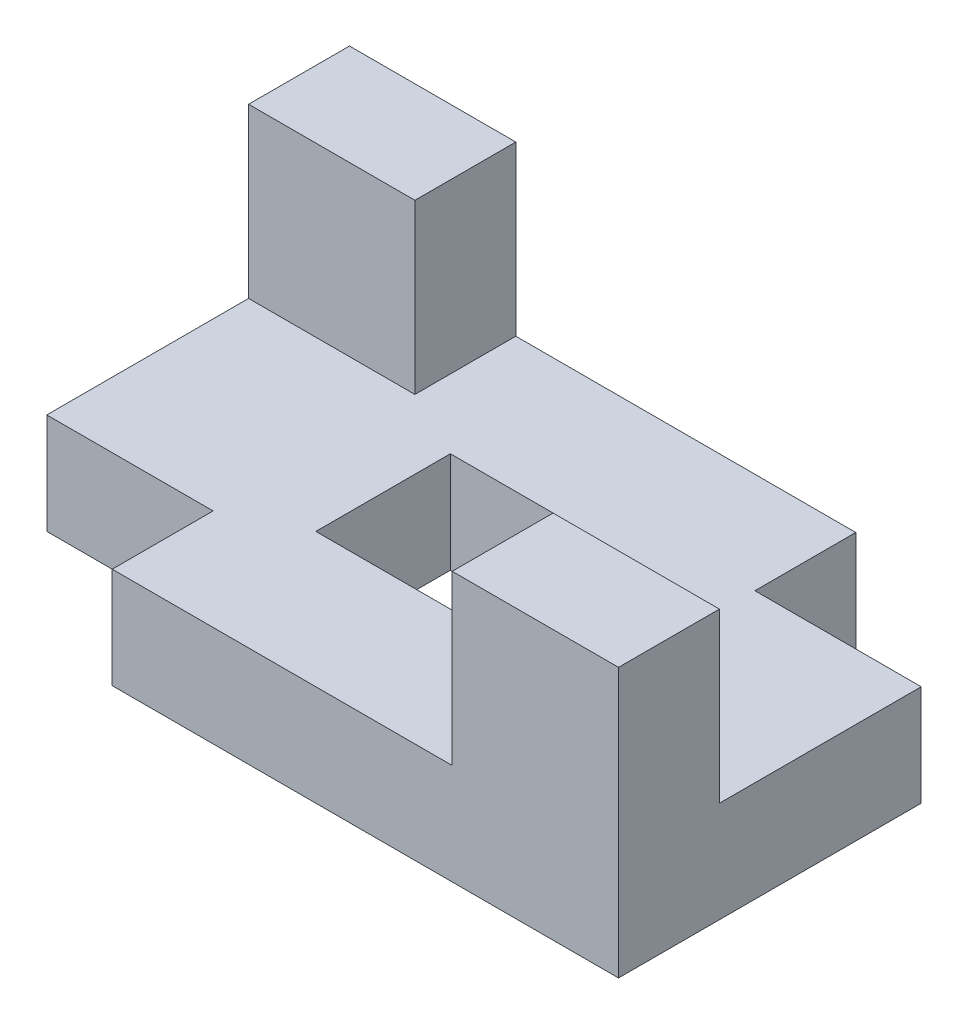
SolidWorks part; units mm, degrees
ref_plane "Front Plane" through (0, 0, 0) normal (0, 0, 1) x (1, 0, 0)
ref_plane "Top Plane" through (0, 0, 0) normal (0, 1, 0) x (1, 0, 0)
ref_plane "Right Plane" through (0, 0, 0) normal (1, 0, 0) x (0, 0, -1)
sketch "Sketch1" plane through (0, 0, 0) normal (0, 1, 0) x (1, 0, 0)
  line L0 (0, 0) -> (0, 61.2785) construction
  line L1 (-50, 30) -> (50, 30)
  line L2 (-50, 30) -> (-50, -30)
  line L3 (-50, -30) -> (50, -30)
  line L4 (50, 30) -> (50, -30)
  line L5 (-50, 30) -> (-25.2735, 30)
  line L6 (-50, 30) -> (-50, 15)
  line L7 (-50, 15) -> (-25.2735, 15)
  line L8 (-25.2735, 30) -> (-25.2735, 15)
  line L9 (0, 0) -> (147.7716, 0) construction
  line L10 (50, 15) -> (25.2735, 15)
  line L11 (25.2735, 30) -> (25.2735, 15)
  line L12 (50, 30) -> (25.2735, 30)
  line L13 (50, 30) -> (50, 15)
  line L14 (50, -30) -> (25.2735, -30)
  line L15 (25.2735, -30) -> (25.2735, -15)
  line L16 (50, -15) -> (25.2735, -15)
  line L17 (50, -30) -> (50, -15)
  line L18 (-50, -15) -> (-25.2735, -15)
  line L19 (-25.2735, -30) -> (-25.2735, -15)
  line L20 (-50, -30) -> (-25.2735, -30)
  line L21 (-50, -30) -> (-50, -15)
  line L23 (-15, 10) -> (15, 10)
  line L24 (-15, 10) -> (-15, -10)
  line L25 (-15, -10) -> (15, -10)
  line L26 (15, 10) -> (15, -10)
  dimension "D1" = 50
  dimension "D2" = 30
  dimension "D3" = 100
  dimension "D4" = 60
  dimension "D5" = 24.7265
  dimension "D6" = 15
  dimension "D7" = 35
  dimension "D8" = 20
  dimension "D9" = 30
  dimension "D10" = 20
extrude "Boss-Extrude1" add sketch "Sketch1" along normal blind 15 contours L8 L1 L2 L7 | L19 L3 L15 L16 L4 L10 L11 L1 L8 L7 L2 L18 L23 L26 L25 L24 | L26 L23 L24 L25 | L1 L11 L10 L4 | L4 L16 L15 L3 | L3 L19 L18 L2 region at (-37.6368, 0, -22.5) region at (0, 0, -28.8338) region at (37.6368, 0, -22.5) region at (-37.6368, 0, 22.5) region at (37.6368, 0, 22.5) region at (0, 0, 0)
extrude "Boss-Extrude2" add sketch "Sketch1<4>" along normal blind 40 contours L6 L7 L8 L5 | L17 L16 L15 L14
sketch "Sketch1<4>" plane through (0, 0, 0) normal (0, 1, 0) x (1, 0, 0) same geometry as "Sketch1"
extrude "Cut-Extrude1" cut sketch "Sketch1<5>" along normal blind 40 contours L3 L19 L18 L2 | L1 L11 L10 L4 region at (37.6368, 0, -22.5) region at (-37.6368, 0, 22.5)
sketch "Sketch1<5>" plane through (0, 0, 0) normal (0, 1, 0) x (1, 0, 0) same geometry as "Sketch1"
extrude "Cut-Extrude2" cut sketch "Sketch1<6>" along normal blind 40 contours L23 L26 L25 L24
sketch "Sketch1<6>" plane through (0, 0, 0) normal (0, 1, 0) x (1, 0, 0) same geometry as "Sketch1"
